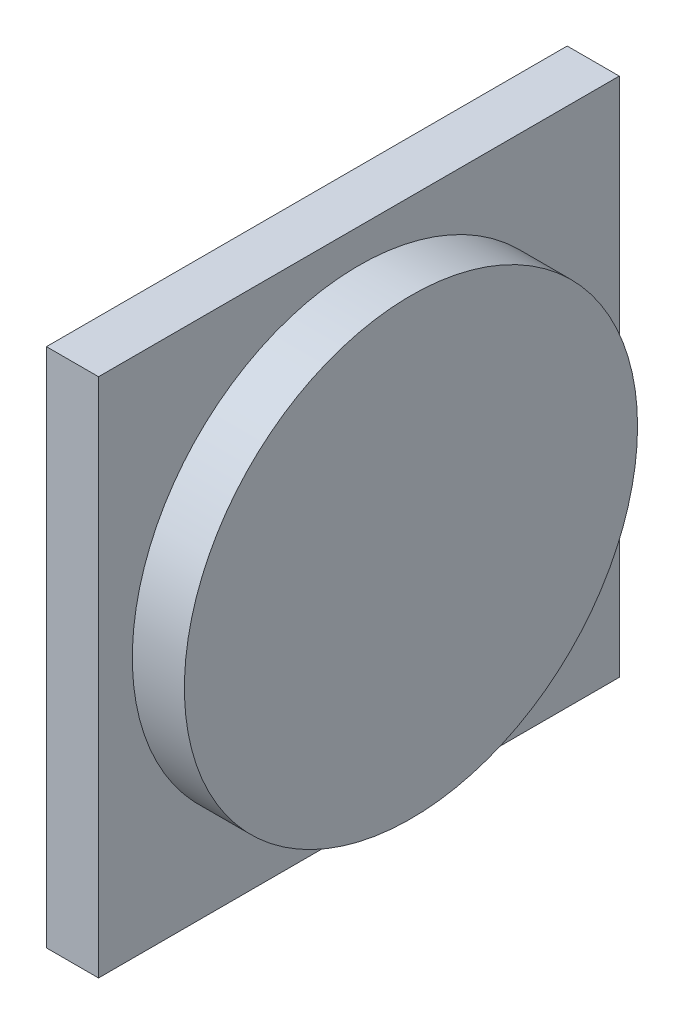
SolidWorks part; units mm, degrees
ref_plane "Ebene vorne" through (0, 0, 0) normal (0, 0, 1) x (1, 0, 0)
ref_plane "Ebene oben" through (0, 0, 0) normal (0, 1, 0) x (1, 0, 0)
ref_plane "Ebene rechts" through (0, 0, 0) normal (1, 0, 0) x (0, 0, -1)
sketch "Sketch1" plane through (0, 0, 0) normal (1, 0, 0) x (0, 0, -1)
  line L1 (0, 0) -> (10, 0)
  line L2 (0, 0) -> (0, 10)
  line L3 (0, 10) -> (10, 10)
  line L4 (10, 0) -> (10, 10)
  dimension "D1" = 10
  dimension "D2" = 10
extrude "Boss-Extrude1" add sketch "Sketch1" along normal blind 1 contours L4 L3 L2 L1
sketch "Sketch2" plane through (1, 0, 0) normal (1, 0, 0) x (0, 0, -1)
  line L0 (0, 10) -> (10, 0) construction
  line L1 (10, 10) -> (0, 0) construction
  circle A0 centre (5, 5) radius 4.3512
extrude "Boss-Extrude2" add sketch "Sketch2" along normal blind 1
